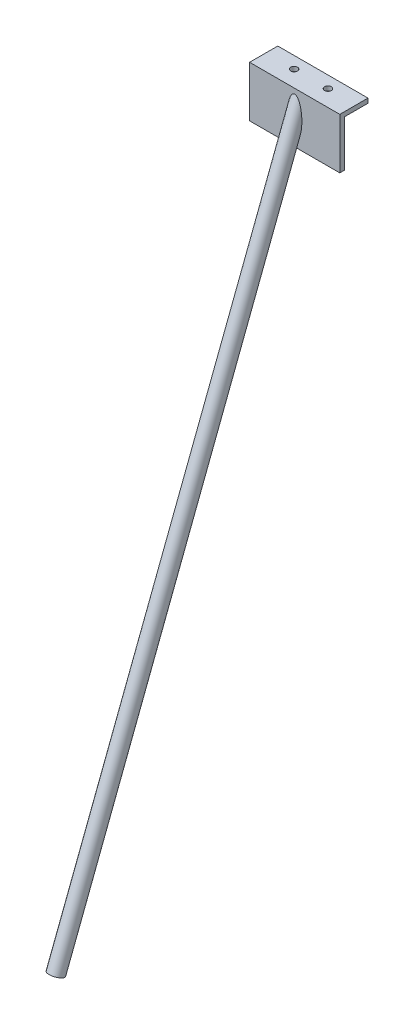
SolidWorks part; units mm, degrees
ref_plane "Front Plane" through (0, 0, 0) normal (0, 0, 1) x (1, 0, 0)
ref_plane "Top Plane" through (0, 0, 0) normal (0, 1, 0) x (1, 0, 0)
ref_plane "Right Plane" through (0, 0, 0) normal (1, 0, 0) x (0, 0, -1)
sketch "Sketch1" plane through (0, 0, 0) normal (1, 0, 0) x (0, 0, -1)
  line L0 (0, 0) -> (25, 0)
  line L1 (25, 0) -> (25, -4)
  line L2 (25, -4) -> (4, -4)
  line L3 (4, -4) -> (4, -45)
  line L4 (4, -45) -> (0, -45)
  line L5 (0, -45) -> (0, 0)
  dimension "D1" = 25
  dimension "D2" = 4
  dimension "D3" = 45
  dimension "D4" = 4
extrude "Boss-Extrude1" add sketch "Sketch1" along normal blind 80
ref_plane "Plane1" through (0, -39.2208, 15.0554) normal (0, 0.9336, -0.3584) x (-1, 0, 0)
sketch "Sketch2" plane through (0, -39.2208, 15.0554) normal (0, 0.9336, -0.3584) x (-1, 0, 0)
  line L0 (-80, -16.1266) -> (0, -16.1266) construction
  circle A0 centre (-40, -8) radius 6.375
  circle A1 centre (-40, -8) radius 4.9
  point P8 (-40, -16.1266)
  dimension "D1" = 12.75
  dimension "D2" = 9.8
extrude "Boss-Extrude2" add sketch "Sketch2" along normal up to surface and the other way blind 570 up to face at (40, -22.5, 0)
hole_wizard "Ø6.0mm Dowel Hole1" positions "Sketch3" profile "Sketch4" hole size "Ø6.0" standard "ISO" end condition through all
sketch "Sketch3" plane through (0, 0, 0) normal (0, 1, 0) x (1, 0, 0)
  line L1 (80, 25) -> (0, 25) construction
  line L4 (25, 14.5) -> (55, 14.5) construction
  point P0 (25, 14.5)
  point P2 (55, 14.5)
  point P23 (40, 14.5)
  point P24 (40, 25)
  dimension "D1" = 10.5
  dimension "D3" = 30
sketch "Sketch4" plane through (25, 0, -14.5) normal (1, 0, 0) x (0, 0, 1)
  line L0 (0, 0) -> (0, 576.5131)
  line L1 (0, 576.5131) -> (3, 576.5131)
  line L2 (3, 576.5131) -> (3, 0)
  line L5 (3, 0) -> (0, 0)
  line L11 (0, -6.35) -> (0, 107.95) construction
  dimension "Thru Hole Dia." = 6
  dimension "Thru Hole Depth" = 576.5131
equation "\"D4@Sketch1\"=\"D2@Sketch1\""
